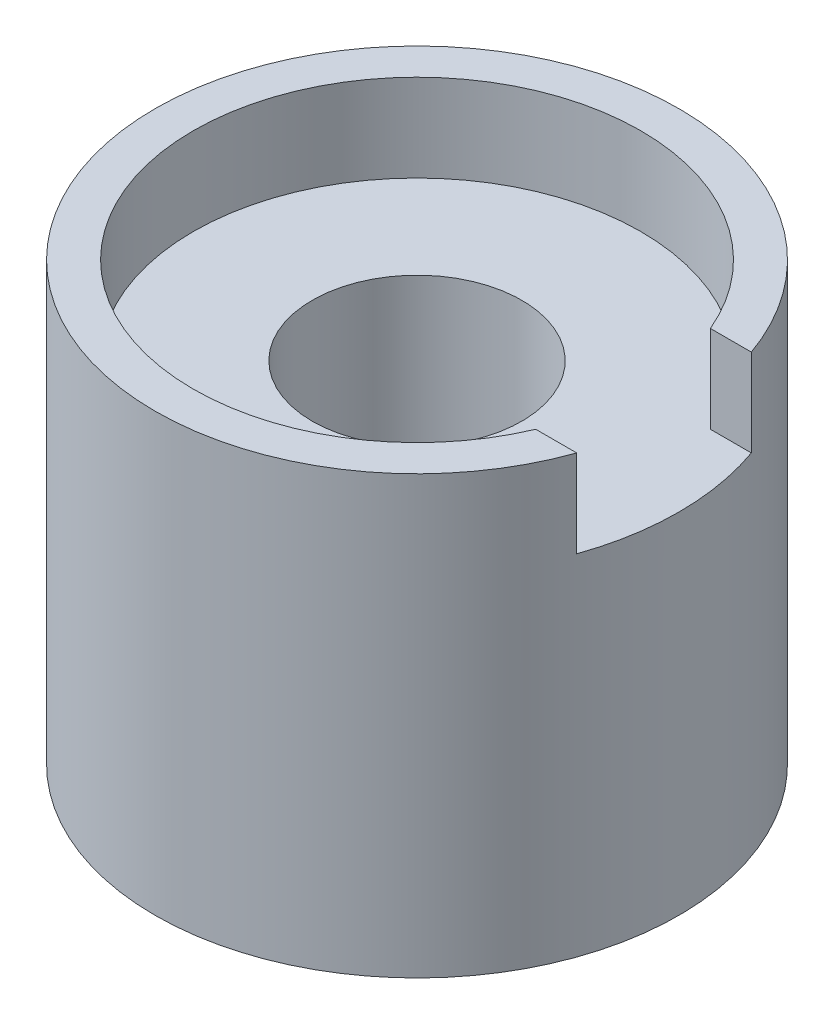
SolidWorks part; units mm, degrees
ref_plane "Front Plane" through (0, 0, 0) normal (0, 0, 1) x (1, 0, 0)
ref_plane "Top Plane" through (0, 0, 0) normal (0, 1, 0) x (1, 0, 0)
ref_plane "Right Plane" through (0, 0, 0) normal (1, 0, 0) x (0, 0, -1)
sketch "Sketch1" plane through (0, 0, 0) normal (0, 1, 0) x (1, 0, 0)
  circle A0 centre (0, 0) radius 12
  circle A1 centre (0, 0) radius 4.8
extrude "Boss-Extrude2" add sketch "Sketch1" against normal blind 20 contours A0 A1 | A1 region at (-11.6606, 0, 0) region at (0, 0, 0)
extrude "Cut-Extrude2" cut sketch "Sketch1<3>" against normal through all contours A1 region at (0, 0, 0)
sketch "Sketch1<3>" plane through (0, 0, 0) normal (0, 1, 0) x (1, 0, 0) same geometry as "Sketch1"
sketch "Sketch3" plane through (0, 0, 0) normal (0, 1, 0) x (1, 0, 0)
  circle A0 centre (0, 0) radius 10.25
extrude "Cut-Extrude3" cut sketch "Sketch3" against normal blind 4
sketch "Sketch5" plane through (0, 0, 0) normal (0, 1, 0) x (1, 0, 0)
  line L0 (-55, 0) -> (55, 0) construction
  line L1 (5.4486, -4) -> (16.4836, -4)
  line L2 (5.4486, -4) -> (5.4486, 4)
  line L3 (5.4486, 4) -> (16.4836, 4)
  line L4 (16.4836, -4) -> (16.4836, 4)
  line L5 (5.4486, -4) -> (16.4836, 4) construction
  line L6 (5.4486, 4) -> (16.4836, -4) construction
  point P0 (10.9661, 0)
  dimension "D1" = 8
extrude "Cut-Extrude5" cut sketch "Sketch5" against normal up to surface (4 mm away) up to face at (0, -4, 10.25)
